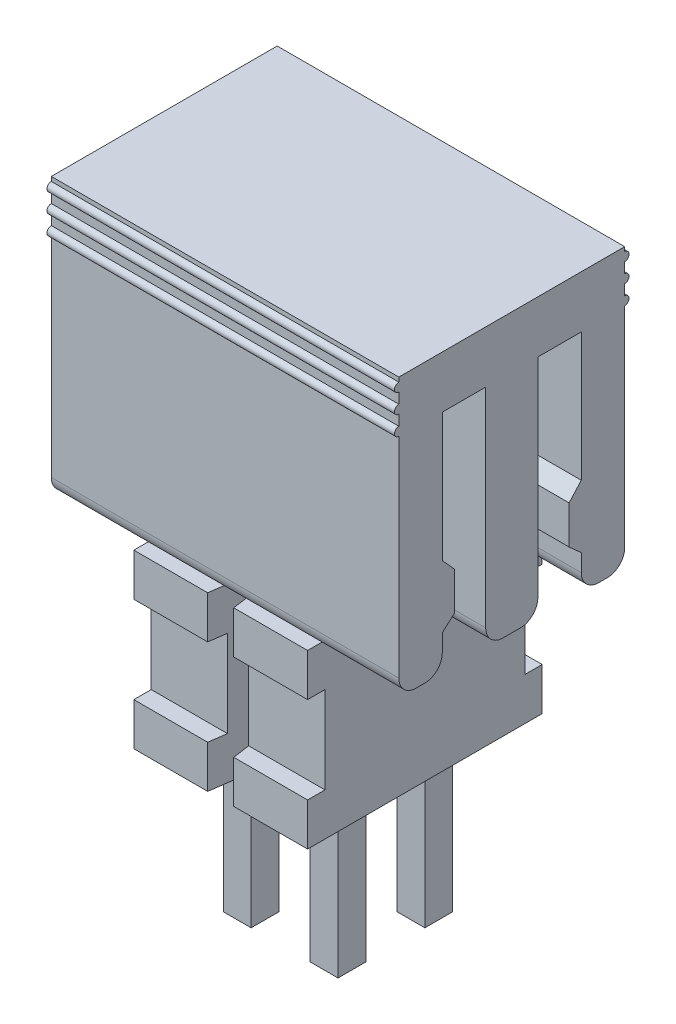
SolidWorks part; units mm, degrees
ref_plane "Front" through (0, 0, 0) normal (0, 0, 1) x (1, 0, 0)
ref_plane "Top" through (0, 0, 0) normal (0, 1, 0) x (1, 0, 0)
ref_plane "Side" through (0, 0, 0) normal (1, 0, 0) x (0, 0, -1)
sketch "Sketch1" plane through (0, 0, 0) normal (0, 1, 0) x (1, 0, 0)
  line L0 (1.27, -1.7145) -> (-1.27, 1.7145) construction
  line L1 (-1.27, 1.7145) -> (1.27, 1.7145)
  line L2 (-1.27, 1.7145) -> (-1.27, -1.7145)
  line L3 (-1.27, -1.7145) -> (1.27, -1.7145)
  line L4 (1.27, 1.7145) -> (1.27, -1.7145)
  dimension "D1" = 3.429
  dimension "D2" = 2.54
extrude "Base" add sketch "Sketch1" along normal blind 2.5146
sketch "Sketch2" plane through (0, 2.5146, 0) normal (0, 1, 0) x (-1, 0, 0)
  line L0 (1.27, 0) -> (3.879, 0) construction
  line L1 (1.27, -1.7145) -> (1.27, 1.7145) construction
  line L2 (0.1905, 1.7145) -> (0.1016, 1.0795)
  line L3 (1.27, 1.7145) -> (-1.27, 1.7145) construction
  line L4 (0.1016, 1.0795) -> (-0.1016, 1.0795)
  line L5 (-0.1016, 1.0795) -> (-0.1905, 1.7145)
  line L6 (-0.1905, 1.7145) -> (0.1905, 1.7145)
  line L7 (0, 1.0795) -> (0, 1.7145) construction
  line L8 (-0.1905, -1.7145) -> (0.1905, -1.7145)
  line L9 (-0.1016, -1.0795) -> (-0.1905, -1.7145)
  line L10 (0.1016, -1.0795) -> (-0.1016, -1.0795)
  line L11 (0.1905, -1.7145) -> (0.1016, -1.0795)
  dimension "D1" = 0.635
  dimension "D2" = 0.2032
  dimension "D3" = 0.381
  dimension "D4" = 1.27
extrude "Snap Groove" cut sketch "Sketch2" against normal through all
sketch "Sketch3" plane through (-1.27, 0, 0) normal (-1, 0, 0) x (0, 0, 1)
  line L0 (-1.7145, 2.5146) -> (-1.7145, 0) construction
  line L1 (-1.7145, 1.8923) -> (-1.4605, 1.8923)
  line L2 (-1.7145, 1.8923) -> (-1.7145, 0.6223)
  line L3 (-1.7145, 0.6223) -> (-1.4605, 0.6223)
  line L4 (-1.4605, 1.8923) -> (-1.4605, 0.6223)
  line L5 (0, 0) -> (0, 2.5146) construction
  line L6 (-1.7145, 2.5146) -> (1.7145, 2.5146) construction
  line L7 (1.4605, 1.8923) -> (1.4605, 0.6223)
  line L8 (1.7145, 0.6223) -> (1.4605, 0.6223)
  line L9 (1.7145, 1.8923) -> (1.7145, 0.6223)
  line L10 (1.7145, 1.8923) -> (1.4605, 1.8923)
  line L11 (-1.7145, 1.2573) -> (1.7145, 1.2573) construction
  line L12 (1.7145, 2.5146) -> (1.7145, 0) construction
  line L13 (-1.4605, 1.2573) -> (1.4605, 1.2573) construction
  dimension "D1" = 2.921
  dimension "D2" = 1.27
extrude "Side Groove" cut sketch "Sketch3" against normal through all
ref_plane "Pos 1 Plane" through (-0.635, 0, 0) normal (-1, 0, 0) x (0, 0, 1)
sketch "Sketch4" plane through (-0.635, 0, 0) normal (-1, 0, 0) x (0, 0, 1)
  line L0 (-1.7145, 2.5146) -> (1.7145, 2.5146) construction
  line L1 (0.8382, 2.5146) -> (0.4318, 2.5146)
  line L2 (0.8382, 2.5146) -> (0.8382, 5.5626)
  line L3 (0.8382, 5.5626) -> (0.4318, 5.5626)
  line L4 (0.4318, 2.5146) -> (0.4318, 5.5626)
  line L5 (0, 0) -> (0, 2.5146) construction
  line L6 (-0.4318, 2.5146) -> (-0.4318, 5.5626)
  line L7 (-0.8382, 5.5626) -> (-0.4318, 5.5626)
  line L8 (-0.8382, 2.5146) -> (-0.8382, 5.5626)
  line L9 (-0.8382, 2.5146) -> (-0.4318, 2.5146)
  line L10 (0.635, 2.5146) -> (0.635, 5.5626) construction
  dimension "D1" = 0.4064
  dimension "D2" = 3.048
  dimension "D3" = 0.635
extrude "Pin Post" add sketch "Sketch4" along normal mid plane 0.4064
chamfer "Post Tip" distance 0.2286 angle 30 8 edges at (-0.4318, 5.5626, -0.635) (-0.635, 5.5626, -0.8382) (-0.8382, 5.5626, -0.635) (-0.635, 5.5626, -0.4318) (-0.4318, 5.5626, 0.635) (-0.635, 5.5626, 0.4318) (-0.8382, 5.5626, 0.635) (-0.635, 5.5626, 0.8382) first distance on face at (-0.4318, 4.0386, -0.635) first distance on face at (-0.635, 4.0386, -0.8382) first distance on face at (-0.8382, 4.0386, -0.635) first distance on face at (-0.635, 4.0386, -0.4318) first distance on face at (-0.4318, 4.0386, 0.635) first distance on face at (-0.635, 4.0386, 0.4318) first distance on face at (-0.8382, 4.0386, 0.635) first distance on face at (-0.635, 4.0386, 0.8382)
pattern_linear "Post Pattern" count 2 spacing 1.27 along (1, 0, 0) of "Pin Post", "Post Tip"
sketch "Sketch5" plane through (-0.635, 0, 0) normal (-1, 0, 0) x (0, 0, 1)
  line L0 (-1.7145, 0) -> (1.7145, 0) construction
  line L1 (0.4318, 0) -> (0.8382, 0)
  line L2 (0.4318, 0) -> (0.4318, -2.286)
  line L3 (0.4318, -2.286) -> (0.8382, -2.286)
  line L4 (0.8382, 0) -> (0.8382, -2.286)
  line L5 (0, 0) -> (0, 2.5146) construction
  line L6 (-1.7145, 2.5146) -> (1.7145, 2.5146) construction
  line L7 (0.635, 0) -> (0.635, -2.286) construction
  line L8 (-0.8382, 0) -> (-0.8382, -2.286)
  line L9 (-0.4318, -2.286) -> (-0.8382, -2.286)
  line L10 (-0.4318, 0) -> (-0.4318, -2.286)
  line L11 (-0.4318, 0) -> (-0.8382, 0)
  line L13 (0.4318, 5.334) -> (0.4318, 2.5146) construction
  dimension "D1" = 0.4064
  dimension "D2" = 2.286
extrude "-TH Tail" add sketch "Sketch5" along normal mid plane 0.4064
pattern_linear "-TH Tail Pattern" count 2 spacing 1.27 along (1, 0, 0) of "-TH Tail"
sketch "Sketch23" plane through (-0.635, 0, 0) normal (-1, 0, 0) x (0, 0, 1)
  line L0 (0.4318, 0) -> (2.921, 0)
  line L1 (-1.7145, 0) -> (1.7145, 0) construction
  line L2 (2.921, 0) -> (2.921, -0.4064)
  line L3 (2.921, -0.4064) -> (1.0242, -0.4064)
  line L4 (0, 0) -> (0, -0.8121) construction
  line L5 (-2.921, -0.4064) -> (-1.0242, -0.4064)
  line L6 (-2.921, 0) -> (-2.921, -0.4064)
  line L7 (-0.4318, 0) -> (-2.921, 0)
  line L8 (0.4318, 5.334) -> (0.4318, 2.5146) construction
  arc A0 (1.0242, -0.4064) -> (0.4318, 0) centre (1.0242, 0.2286) cw
  arc A1 (-1.0242, -0.4064) -> (-0.4318, 0) centre (-1.0242, 0.2286) ccw
  dimension "D2" = 0.635
  dimension "D1" = 0.4064
  dimension "D3" = 5.842
sketch "Sketch29" plane through (-0.635, 0, 0) normal (-1, 0, 0) x (0, 0, 1)
  line L0 (0.8382, 0) -> (0.8382, -0.608)
  line L1 (-1.7145, 0) -> (1.7145, 0) construction
  line L2 (1.7145, -1.778) -> (1.7145, -2.286)
  line L3 (1.7145, 0.6223) -> (1.7145, 0) construction
  line L4 (0.8382, 2.5146) -> (0.8382, 5.334) construction
  line L5 (0.4318, 0) -> (0.4318, -0.608)
  line L6 (1.3081, -1.778) -> (1.3081, -2.286)
  line L7 (0.8382, 0) -> (0.4318, 0)
  line L8 (1.7145, -2.286) -> (1.3081, -2.286)
  line L9 (-0.4318, 0) -> (-0.4318, -2.54)
  line L10 (-0.235, -2.8882) -> (1.3209, -3.8248)
  line L11 (1.7145, -4.5212) -> (1.7145, -5.334)
  line L12 (-0.4318, 2.5146) -> (-0.4318, 5.334) construction
  line L13 (-0.8382, 0) -> (-0.8382, -2.54)
  line L14 (-0.4446, -3.2364) -> (1.1113, -4.173)
  line L15 (1.3081, -4.5212) -> (1.3081, -5.334)
  line L16 (-0.4318, 0) -> (-0.8382, 0)
  line L17 (1.7145, -5.334) -> (1.3081, -5.334)
  arc A0 (0.8382, -0.608) -> (1.1303, -0.998) centre (1.2446, -0.608) ccw
  arc A1 (1.1303, -0.998) -> (1.7145, -1.778) centre (0.9017, -1.778) cw
  arc A2 (0.4318, -0.608) -> (1.016, -1.388) centre (1.2446, -0.608) ccw
  arc A3 (1.016, -1.388) -> (1.3081, -1.778) centre (0.9017, -1.778) cw
  arc A4 (-0.4318, -2.54) -> (-0.235, -2.8882) centre (-0.0254, -2.54) ccw
  arc A5 (1.3209, -3.8248) -> (1.7145, -4.5212) centre (0.9017, -4.5212) cw
  arc A6 (-0.8382, -2.54) -> (-0.4446, -3.2364) centre (-0.0254, -2.54) ccw
  arc A7 (1.1113, -4.173) -> (1.3081, -4.5212) centre (0.9017, -4.5212) cw
  dimension "D3" = 0.4064
  dimension "D4" = 0.8128
  dimension "D8" = 0.4064
  dimension "D9" = 0.8128
  dimension "D1" = 2.286
  dimension "D2" = 0.508
  dimension "D6" = 0.8128
  dimension "D7" = 5.334
  dimension "D10" = 2.54
  dimension "D5" = 0.4064
  dimension "D11" = 0.4064
sketch "Sketch33" plane through (-0.635, 0, 0) normal (-1, 0, 0) x (0, 0, 1)
  line L0 (-0.4318, 0) -> (-0.4318, -2.54)
  line L1 (-1.7145, 0) -> (1.7145, 0) construction
  line L2 (-0.235, -2.8882) -> (1.3209, -3.8248)
  line L3 (1.7145, -4.5212) -> (1.7145, -5.334)
  line L4 (1.7145, 0.6223) -> (1.7145, 0) construction
  line L5 (-0.8382, 0) -> (-0.8382, -2.54)
  line L6 (-0.4446, -3.2364) -> (1.1113, -4.173)
  line L7 (1.3081, -4.5212) -> (1.3081, -5.334)
  line L8 (1.7145, -5.334) -> (1.3081, -5.334)
  line L9 (-0.8382, 0) -> (-0.4318, 0)
  line L10 (0.8382, 0) -> (0.8382, -0.6604)
  line L11 (1.2446, -1.0668) -> (4.0005, -1.0668)
  line L12 (0.4318, 0) -> (0.4318, -0.6604)
  line L13 (1.2446, -1.4732) -> (4.0005, -1.4732)
  line L14 (0.4318, 0) -> (0.8382, 0)
  line L15 (4.0005, -1.4732) -> (4.0005, -1.0668)
  arc A0 (-0.4318, -2.54) -> (-0.235, -2.8882) centre (-0.0254, -2.54) ccw
  arc A1 (1.3209, -3.8248) -> (1.7145, -4.5212) centre (0.9017, -4.5212) cw
  arc A2 (-0.8382, -2.54) -> (-0.4446, -3.2364) centre (-0.0254, -2.54) ccw
  arc A3 (1.1113, -4.173) -> (1.3081, -4.5212) centre (0.9017, -4.5212) cw
  arc A4 (0.8382, -0.6604) -> (1.2446, -1.0668) centre (1.2446, -0.6604) ccw
  arc A5 (0.4318, -0.6604) -> (1.2446, -1.4732) centre (1.2446, -0.6604) ccw
  dimension "D1" = 0.4064
  dimension "D2" = 0.8128
  dimension "D5" = 2.54
  dimension "D7" = 0.4064
  dimension "D3" = 0.8128
  dimension "D4" = 5.334
  dimension "D8" = 1.0668
  dimension "D9" = 2.286
  dimension "D6" = 0.4064
  dimension "D10" = 0.4064
sketch "Sketch6" plane through (0, 0, 0) normal (0, -1, 0) x (1, 0, 0)
  line L0 (-1.27, -1.7145) -> (-1.27, 1.7145) construction
  line L1 (0, 0) -> (0, 1.567) construction
  circle A0 centre (0, 0) radius 0.4445
  circle A1 centre (0, 0) radius 0.4445
  dimension "D1" = 0.889
  dimension "D2" = 1.27
sketch "Sketch28" plane through (0, 0, 1.0795) normal (0, 0, 1) x (1, 0, 0)
  line L0 (0, 0) -> (0, 1.9421) construction
  line L2 (-1.27, 1.2573) -> (-1.1251, 1.2573) construction
  line L3 (-1.27, 1.8923) -> (-1.27, 0.6223) construction
  circle A0 centre (0, 1.2573) radius 0.4445
  circle A1 centre (0, 1.2573) radius 0.4445
  dimension "D1" = 0.889
  dimension "D2" = 1.27
sketch "Sketch16" plane through (0, 0, 0) normal (0, -1, 0) x (1, 0, 0)
  line L1 (-2.54, 1.7145) -> (2.54, 1.7145)
  line L2 (-2.54, 1.7145) -> (-2.54, 2.54)
  line L3 (-2.54, 2.54) -> (2.54, 2.54)
  line L4 (2.54, 1.7145) -> (2.54, 2.54)
  line L5 (0, 0) -> (1.4804, 0) construction
  line L6 (2.54, -1.7145) -> (2.54, -2.54)
  line L7 (-2.54, -2.54) -> (2.54, -2.54)
  line L8 (-2.54, -1.7145) -> (-2.54, -2.54)
  line L9 (-2.54, -1.7145) -> (2.54, -1.7145)
  line L10 (0, 2.54) -> (0, 1.7145) construction
  line L11 (-1.27, 1.7145) -> (-0.1905, 1.7145) construction
  dimension "D1" = 5.08
  dimension "D2" = 5.08
ref_plane "Shroud Plane" through (0, 0.254, 0) normal (0, -1, 0) x (1, 0, 0)
sketch "Sketch7" plane through (0, 0.254, 0) normal (0, -1, 0) x (1, 0, 0)
  line L0 (4.1783, -1.7653) -> (-1.4097, -1.7653)
  line L1 (-1.4097, -1.7653) -> (-1.4097, 1.7653)
  line L3 (4.1783, 1.7653) -> (4.1783, 2.3876)
  line L4 (4.1783, 2.3876) -> (-2.5527, 2.3876)
  line L5 (-2.5527, 2.3876) -> (-2.5527, -2.3876)
  line L6 (-2.5527, -2.3876) -> (4.1783, -2.3876)
  line L7 (4.1783, -2.3876) -> (4.1783, -1.7653)
  line L8 (-1.4097, 0) -> (-2.5527, 0) construction
  line L9 (-1.4097, 0) -> (-5.1743, 0) construction
  line L10 (-1.27, -1.7145) -> (-1.27, 1.7145) construction
  line L14 (-1.4097, 1.7653) -> (4.1783, 1.7653)
  dimension "D1" = 3.5306
  dimension "D2" = 6.731
  dimension "D3" = 1.143
  dimension "D4" = 4.7752
  dimension "D5" = 1.2827
ref_axis "-EL Axis1" through (0, 6.9279, 0) along (0, -1, 0)
sketch "Sketch24" plane through (0, 0, 0) normal (1, 0, 0) x (0, 0, -1)
  line L0 (-1.016, 5.8166) -> (-1.016, 3.939)
  line L1 (-1.016, 3.939) -> (-0.8382, 3.7415)
  line L2 (-0.8382, 3.7415) -> (-0.8382, 3.1827)
  line L3 (-0.8382, 3.1827) -> (-1.016, 3.0226)
  line L4 (-1.016, 3.0226) -> (-1.016, 2.7686)
  line L5 (-1.27, 2.5146) -> (-1.397, 2.5146)
  line L6 (-1.651, 2.7686) -> (-1.651, 5.8166)
  line L7 (0, 0) -> (0, 5.5673) construction
  line L8 (1.651, 2.7686) -> (1.651, 5.8166)
  line L9 (1.27, 2.5146) -> (1.397, 2.5146)
  line L10 (1.016, 3.0226) -> (1.016, 2.7686)
  line L11 (0.8382, 3.1827) -> (1.016, 3.0226)
  line L12 (0.8382, 3.7415) -> (0.8382, 3.1827)
  line L13 (1.016, 3.939) -> (0.8382, 3.7415)
  line L14 (1.016, 5.8166) -> (1.016, 3.939)
  line L15 (-1.7145, 2.5146) -> (1.7145, 2.5146) construction
  line L16 (1.016, 5.8166) -> (0.381, 5.8166)
  line L17 (-1.651, 5.8166) -> (-2.921, 5.8166)
  line L18 (-0.381, 5.8166) -> (-1.016, 5.8166)
  line L19 (2.921, 6.5786) -> (-2.921, 6.5786)
  line L20 (2.921, 6.5786) -> (2.921, 5.8166)
  line L21 (2.921, 5.8166) -> (1.651, 5.8166)
  line L22 (-2.921, 6.5786) -> (-2.921, 5.8166)
  line L24 (-0.381, 5.8166) -> (-0.381, 2.7686)
  line L25 (-0.127, 2.5146) -> (0.127, 2.5146)
  line L26 (0.381, 5.8166) -> (0.381, 2.7686)
  arc A0 (1.397, 2.5146) -> (1.651, 2.7686) centre (1.397, 2.7686) ccw
  arc A1 (1.27, 2.5146) -> (1.016, 2.7686) centre (1.27, 2.7686) cw
  arc A2 (-1.27, 2.5146) -> (-1.016, 2.7686) centre (-1.27, 2.7686) ccw
  arc A3 (-1.397, 2.5146) -> (-1.651, 2.7686) centre (-1.397, 2.7686) cw
  arc A4 (0.381, 2.7686) -> (0.127, 2.5146) centre (0.127, 2.7686) cw
  arc A5 (-0.127, 2.5146) -> (-0.381, 2.7686) centre (-0.127, 2.7686) cw
  point P20 (1.651, 2.5146)
  point P28 (1.016, 2.5146)
  point P31 (-1.016, 2.5146)
  point P34 (-1.651, 2.5146)
  dimension "D10" = 0.254
  dimension "D11" = 0.762
  dimension "D13" = 0.254
  dimension "D1" = 42
  dimension "D2" = 0.508
  dimension "D3" = 0.5588
  dimension "D4" = 0.635
  dimension "D5" = 0.1778
  dimension "D6" = 4.064
  dimension "D7" = 5.842
  dimension "D8" = 3.302
  dimension "D9" = 3.302
  dimension "D12" = 0.762
extrude "-P" add sketch "Sketch24" along normal mid plane 5.08
sketch "Sketch43" plane through (2.54, 0, 0) normal (1, 0, 0) x (0, 0, -1)
  line L0 (-1.651, 5.8293) -> (-1.651, 5.8166)
  line L1 (-2.921, 6.5786) -> (-1.651, 6.5786)
  line L2 (-2.921, 6.5786) -> (-2.921, 5.8166)
  line L3 (-2.921, 5.8166) -> (-1.651, 5.8166)
  line L4 (-1.651, 6.5786) -> (-1.651, 6.5151)
  line L5 (0, 6.5786) -> (0, 5.3215) construction
  line L6 (1.651, 6.3881) -> (1.651, 6.2357)
  line L7 (1.651, 6.1087) -> (1.651, 5.9563)
  line L8 (1.651, 6.5786) -> (1.651, 6.5151)
  line L9 (-1.651, 6.1087) -> (-1.651, 5.9563)
  line L10 (-1.651, 6.3881) -> (-1.651, 6.2357)
  line L11 (2.921, 6.5786) -> (-2.921, 6.5786) construction
  line L12 (2.921, 5.8166) -> (1.651, 5.8166)
  line L13 (2.921, 6.5786) -> (2.921, 5.8166)
  line L14 (2.921, 6.5786) -> (1.651, 6.5786)
  line L15 (1.651, 5.8293) -> (1.651, 5.8166)
  arc A0 (-1.651, 6.5151) -> (-1.651, 6.3881) centre (-1.651, 6.4516) ccw
  arc A1 (-1.651, 6.2357) -> (-1.651, 6.1087) centre (-1.651, 6.1722) ccw
  arc A2 (-1.651, 5.9563) -> (-1.651, 5.8293) centre (-1.651, 5.8928) ccw
  arc A3 (1.651, 5.9563) -> (1.651, 5.8293) centre (1.651, 5.8928) cw
  arc A4 (1.651, 6.2357) -> (1.651, 6.1087) centre (1.651, 6.1722) cw
  arc A5 (1.651, 6.5151) -> (1.651, 6.3881) centre (1.651, 6.4516) cw
  dimension "D1" = 0.127
  dimension "D2" = 0.2794
  dimension "D3" = 0.2794
  dimension "D4" = 0.127
extrude "PPP-25 cut" cut sketch "Sketch43" against normal up to surface (5.08 mm away) up to face at (-2.54, 3.9615, 0)
sketch "Sketch31" plane through (0, 0, -1.7145) normal (0, 0, -1) x (-1, 0, 0)
  line L0 (0, 0) -> (0, 1.6923) construction
  line L5 (0.1905, 2.5146) -> (1.27, 2.5146) construction
  circle A0 centre (0, 1.2586) radius 2.5006
  dimension "D1" = 5.0013
  dimension "D2" = 1.2446
ref_plane "-EJ Plane" through (0, 0, 2.825) normal (0, 0, 1) x (1, 0, 0)
